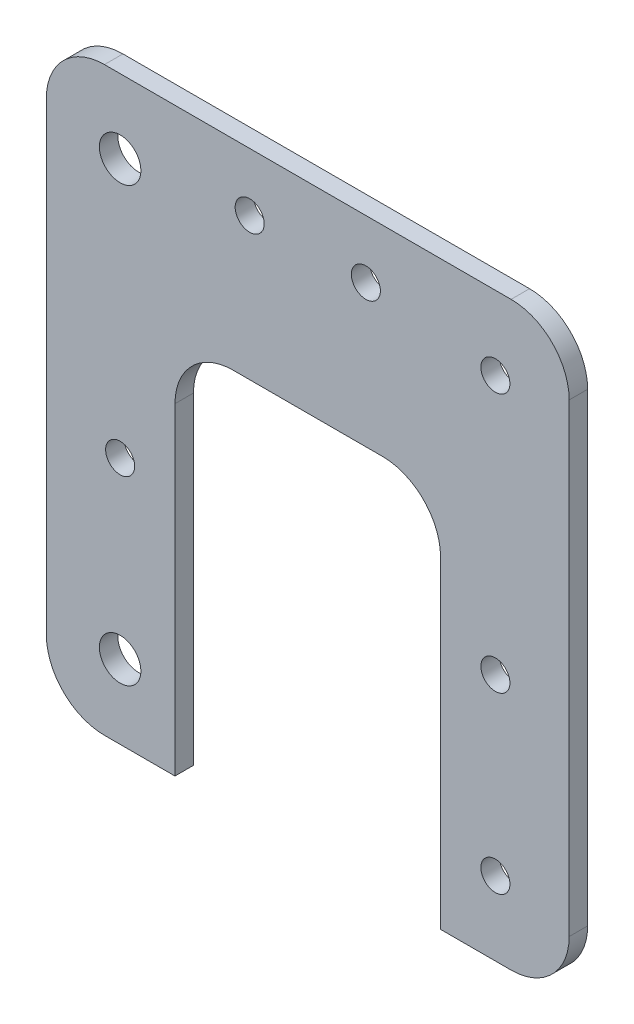
SolidWorks part; units mm, degrees
ref_plane "Front Plane" through (0, 0, 0) normal (0, 0, 1) x (1, 0, 0)
ref_plane "Top Plane" through (0, 0, 0) normal (0, 1, 0) x (1, 0, 0)
ref_plane "Right Plane" through (0, 0, 0) normal (1, 0, 0) x (0, 0, -1)
sketch "Sketch1" plane through (0, 0, 0) normal (0, 0, 1) x (1, 0, 0)
  line L1 (-45, -55) -> (45, -55)
  line L2 (-45, -55) -> (-45, 45)
  line L3 (-45, 45) -> (45, 45)
  line L4 (45, -55) -> (45, 45)
  line L8 (-32.3, 32.3) -> (-32.3, -42.3) construction
  line L9 (-32.3, -42.3) -> (32.3, -42.3) construction
  line L10 (32.3, -42.3) -> (32.3, 32.3) construction
  line L11 (32.3, 32.3) -> (-32.3, 32.3) construction
  line L12 (32.3, -12.3) -> (-32.3, -12.3) construction
  circle A4 centre (32.3, -12.3) radius 2.5
  circle A5 centre (32.3, -42.3) radius 2.5
  circle A6 centre (-32.3, -42.3) radius 3.57
  circle A7 centre (-32.3, -12.3) radius 2.5
  circle A9 centre (-32.3, 32.3) radius 3.57
  circle A11 centre (32.3, 32.3) radius 2.5
  dimension "D9" = 7.14
  dimension "D10" = 5
  dimension "D1" = 90
  dimension "D2" = 100
  dimension "D3" = 12.7
  dimension "D4" = 12.7
  dimension "D5" = 42.7
  dimension "D6" = 12.7
  dimension "D7" = 45
  dimension "D8" = 45
  dimension "D11" = 12.7
extrude "Boss-Extrude1" add sketch "Sketch1" against normal blind 3.18 from offset 19.16
sketch "Sketch2" plane through (0, 0, 15.98) normal (0, 0, -1) x (-1, 0, 0)
  line L0 (45, -55) -> (-45, -55) construction
  line L1 (-22.86, -55) -> (22.86, -55)
  line L2 (-22.86, -55) -> (-22.86, 10.5119)
  line L3 (-22.86, 10.5119) -> (22.86, 10.5119)
  line L4 (22.86, -55) -> (22.86, 10.5119)
  line L5 (0, 0) -> (0, 10.5119) construction
  dimension "D1" = 45.72
extrude "Cut-Extrude1" cut sketch "Sketch2" against normal through all
fillet "Fillet1" radius 10 6 edges at (45, -55, 17.57) (-45, -55, 17.57) (-45, 45, 17.57) (45, 45, 17.57) (-22.86, 10.5119, 17.57) (22.86, 10.5119, 17.57)
ref_plane "Midplane" through (0, -5, 0) normal (0, 1, 0) x (1, 0, 0)
sketch "Sketch3" plane through (0, 0, 19.16) normal (0, 0, 1) x (1, 0, 0)
  circle A0 centre (10, 35) radius 2.5 construction
  circle A1 centre (-10, 35) radius 2.5 construction
  circle A2 centre (10, 35) radius 2.5
  circle A3 centre (-10, 35) radius 2.5
extrude "Cut-Extrude2" cut sketch "Sketch3" against normal through all
